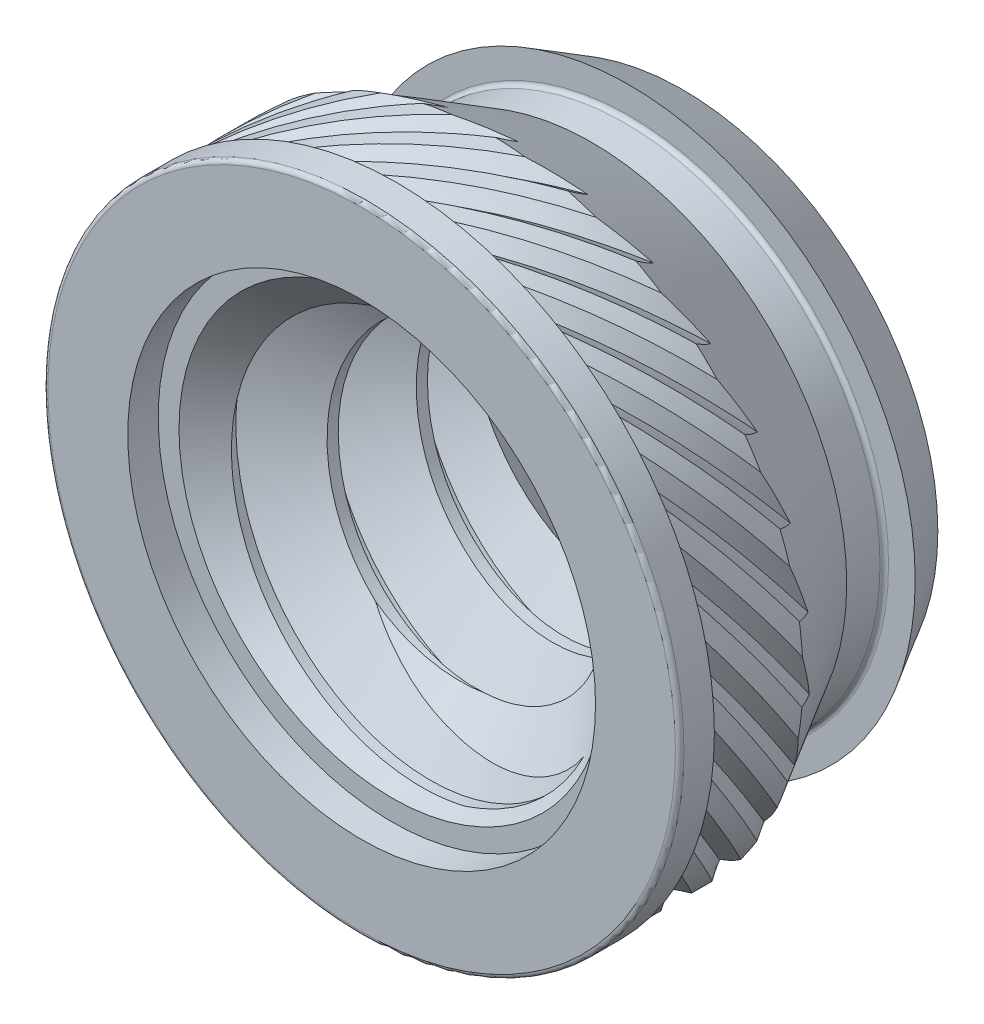
SolidWorks part; units mm, degrees
ref_plane "Front Plane" through (0, 0, 0) normal (0, 0, 1) x (1, 0, 0)
ref_plane "Top Plane" through (0, 0, 0) normal (0, 1, 0) x (1, 0, 0)
ref_plane "Right Plane" through (0, 0, 0) normal (1, 0, 0) x (0, 0, -1)
sketch "Sketch1" plane through (0, 0, 0) normal (1, 0, 0) x (0, 0, -1)
  line L0 (-1.905, 0) -> (1.905, 0) construction
  line L1 (-1.905, 2.413) -> (-1.905, 3.7719)
  line L2 (-1.905, 3.7719) -> (-1.4931, 3.7719)
  line L3 (-1.4931, 3.7719) -> (-1.4931, 3.7338)
  line L4 (-1.4931, 3.7338) -> (-0.4045, 3.7338)
  line L11 (1.27, 3.0243) -> (0.8243, 3.0243)
  line L14 (1.27, 3.0243) -> (1.27, 3.3909)
  line L15 (1.27, 3.3909) -> (1.905, 3.0243)
  line L16 (1.905, 3.0243) -> (1.905, 2.413)
  line L18 (1.905, 0) -> (1.905, 2.413) construction
  line L19 (-1.905, 0) -> (-1.905, 3.7719) construction
  line L21 (-1.905, 2.413) -> (1.905, 2.413)
  line L23 (-2.8972, 2.5276) -> (-2.368, 1.611) construction
  line L25 (-2.368, 1.611) -> (-1.8389, 2.5276) construction
  line L26 (-1.8389, 2.5276) -> (-2.8972, 2.5276) construction
  line L27 (-2.831, 2.413) -> (-1.905, 2.413) construction
  line L28 (-2.368, 2.5276) -> (-2.368, 2.413) construction
  line L29 (-2.368, 2.413) -> (-2.368, 1.7256) construction
  line L30 (-2.368, 1.7256) -> (-2.368, 1.611) construction
  line L31 (-2.4342, 1.7256) -> (-2.3019, 1.7256)
  line L32 (-2.8641, 2.4703) -> (-1.8719, 2.4703)
  line L33 (-2.3019, 1.7256) -> (-1.8719, 2.4703)
  line L34 (-2.4342, 1.7256) -> (-2.8641, 2.4703)
  line L37 (-0.4045, 3.7338) -> (0.8243, 3.0243)
  point P36 (-2.368, 2.4703)
  dimension "Installed Length" = 3.81
  dimension "Dia A" = 7.5438
  dimension "Dia B" = 6.7818
  dimension "Thread Size" = 4.826
  dimension "D6" = 30
  dimension "D8" = 1.0886
  dimension "Thread Pitch" = 1.0583
  dimension "D1" = 0.4119
  dimension "D4" = 0.635
  dimension "D5" = 0.0381
  dimension "D3" = 0.3666
sketch "Sketch2" plane through (0, 0, 0) normal (1, 0, 0) x (0, 0, -1)
  line L0 (-1.905, 2.413) -> (-1.905, 3.7719) construction
  line L1 (-1.905, 3.7719) -> (-1.4931, 3.7719) construction
  line L2 (-1.4931, 3.7719) -> (-1.4931, 3.7338) construction
  line L3 (-1.4931, 3.7338) -> (-0.4045, 3.7338) construction
  line L4 (-1.905, 2.7741) -> (-1.5439, 2.7741)
  line L5 (-1.5439, 2.7741) -> (-1.5439, 2.413)
  line L9 (1.27, 3.0243) -> (0.8243, 3.0243) construction
  line L10 (-0.4045, 3.7338) -> (0.8243, 3.0243) construction
  line L12 (-0.4045, 3.7338) -> (0.8243, 3.0243)
  line L13 (1.27, 3.0243) -> (1.27, 3.3909) construction
  line L14 (1.27, 3.3909) -> (1.905, 3.0243) construction
  line L15 (1.905, 3.0243) -> (1.905, 2.413) construction
  line L16 (-1.905, 2.413) -> (1.905, 2.413) construction
  line L17 (-1.905, 2.7741) -> (-1.905, 3.7211)
  line L18 (-1.8542, 3.7719) -> (-1.4931, 3.7719)
  line L19 (-1.4931, 3.7719) -> (-1.4931, 3.7338)
  line L20 (-1.4931, 3.7338) -> (-0.4045, 3.7338)
  line L26 (1.2192, 3.0243) -> (0.8243, 3.0243)
  line L30 (1.27, 3.0751) -> (1.27, 3.3909)
  line L31 (1.27, 3.3909) -> (1.905, 3.0243)
  line L32 (1.905, 3.0243) -> (1.905, 2.413)
  line L33 (-1.5439, 2.413) -> (1.905, 2.413)
  arc A0 (1.2192, 3.0243) -> (1.27, 3.0751) centre (1.2192, 3.0751) ccw
  arc A1 (-1.905, 3.7211) -> (-1.8542, 3.7719) centre (-1.8542, 3.7211) cw
  dimension "D1" = 0.0508
revolve "Revolve1" add sketch "Sketch2" angle 360 about L0
sketch "Sketch3" plane through (0, 0, 1.905) normal (0, 0, 1) x (1, 0, 0)
  circle A0 centre (0, 0) radius 2.413
curve "Helix/Spiral1" pitch 1.0583 height 9.5758 radius 2.413 centre (0, 0, 1.905) axis (0, 0, -1) start towards (0, 1, 0)
sketch "Sketch4" plane through (0, 0, 0) normal (1, 0, 0) x (0, 0, -1)
  line L0 (-2.4342, 1.7256) -> (-2.3019, 1.7256) construction
  line L1 (-2.4342, 1.7256) -> (-2.8641, 2.4703) construction
  line L2 (-2.8641, 2.4703) -> (-1.8719, 2.4703) construction
  line L3 (-2.3019, 1.7256) -> (-1.8719, 2.4703) construction
  line L4 (-2.4342, 1.7256) -> (-2.3019, 1.7256)
  line L5 (-2.4342, 1.7256) -> (-2.8641, 2.4703)
  line L6 (-2.8641, 2.4703) -> (-1.8719, 2.4703)
  line L7 (-2.3019, 1.7256) -> (-1.8719, 2.4703)
sweep "Sweep1" add profiles "Sketch4" path "Helix/Spiral1"
sketch "Sketch5" plane through (0, 0, 1.5439) normal (0, 0, 1) x (1, 0, 0)
  circle A0 centre (0, 0) radius 2.5276
extrude "Cut-Extrude1" cut sketch "Sketch5" against normal through all draft 45 and the other way through all
extrude "Cut-Extrude2" cut sketch "Sketch5<2>" along normal through all draft 45 and the other way through all from surface starting at face at (3.0243, 0, -1.905)
sketch "Sketch5<2>" plane through (0, 0, 1.5439) normal (0, 0, 1) x (1, 0, 0) same geometry as "Sketch5"
ref_plane "Plane1" through (0, 0, 1.4931) normal (0, 0, 1) x (1, 0, 0)
sketch "Sketch6" plane through (0, 0, 1.4931) normal (0, 0, 1) x (1, 0, 0)
  line L0 (0, 0) -> (0, 3.7338) construction
  line L1 (-0.2605, 3.7247) -> (0, 3.6068)
  line L2 (0.2605, 3.7247) -> (0, 3.6068)
  line L3 (-0.2605, 3.7247) -> (0, 0) construction
  line L4 (0.2605, 3.7247) -> (0, 0) construction
  line L5 (0, 0) -> (-0.4874, 3.7019) construction
  line L6 (0, 0) -> (0.4874, 3.7019) construction
  line L7 (0, 0) -> (1.8669, 3.2336) construction
  line L8 (0, 0) -> (0, -2.5276) construction
  line L9 (0, 0) -> (1.2638, -2.1889) construction
  circle A0 centre (0, 0) radius 3.6068 construction
  circle A1 centre (0, 0) radius 3.7338 construction
  arc A2 (-0.2605, 3.7247) -> (0.2605, 3.7247) centre (0, 0) cw
  circle A3 centre (0, 0) radius 2.5276
  dimension "Knurl Angle" = 8
  dimension "Pattern Angle" = 15
  dimension "Helix Angle" = 30
  dimension "D1" = 30
sketch "Sketch7" plane through (0, 0, 1.4931) normal (0, 0, 1) x (1, 0, 0)
  circle A2 centre (0, 0) radius 3.7338 construction
  circle A3 centre (0, 0) radius 3.7338
curve "Helix/Spiral2" pitch 16.3286 height 1.4968 radius 3.7338 centre (0, 0, 1.4931) axis (0, 0, -1) start towards (0, 1, 0)
sketch "Sketch8" plane through (0, 0, 1.4931) normal (0, 0, 1) x (1, 0, 0)
  line L0 (-0.2605, 3.7247) -> (0, 3.6068) construction
  line L1 (0.2605, 3.7247) -> (0, 3.6068) construction
  line L2 (-0.2605, 3.7247) -> (0, 3.6068)
  line L3 (0.2605, 3.7247) -> (0, 3.6068)
  arc A0 (0.2605, 3.7247) -> (-0.2605, 3.7247) centre (0, 0) ccw construction
  arc A1 (0.2605, 3.7247) -> (-0.2605, 3.7247) centre (0, 0) ccw
sweep "Cut-Sweep1" cut profiles "Sketch8" path "Helix/Spiral2" align with end faces yes
pattern_circular "CirPattern1" count 27 over 360 about axis through (0, 0, 1.905) along (0, 0, -1) of "Cut-Sweep1"
equation "\"D8@Sketch1\"=\"Installed Length@Sketch1\" / 3.5"
equation "\"D4@Helix/Spiral2\" = ( \"D8@Sketch1\" * 1.25 ) * ( 360 / \"Helix Angle@Sketch6\" )"
equation "\"D3@Helix/Spiral2\" = ( \"D8@Sketch1\" * 1.25 ) * 1.1"
equation "\"D1@CirPattern1\"=( \"D3@CirPattern1\" / \"Pattern Angle@Sketch6\" ) * 1.125"
equation "\"D2@Sketch1\" = \"Thread Pitch@Sketch1\" / 8"
equation "\"D4@Helix/Spiral1\" = \"Thread Pitch@Sketch1\""
equation "\"D1@Sketch1\"=\"Installed Length@Sketch1\" / 9.25"
equation "\"D4@Sketch1\"=\"Installed Length@Sketch1\" / 6"
equation "\"D5@Sketch1\"=\"Installed Length@Sketch1\"/100"
equation "\"D3@Sketch1\" = \"Dia B@Sketch1\" / 18.5"
